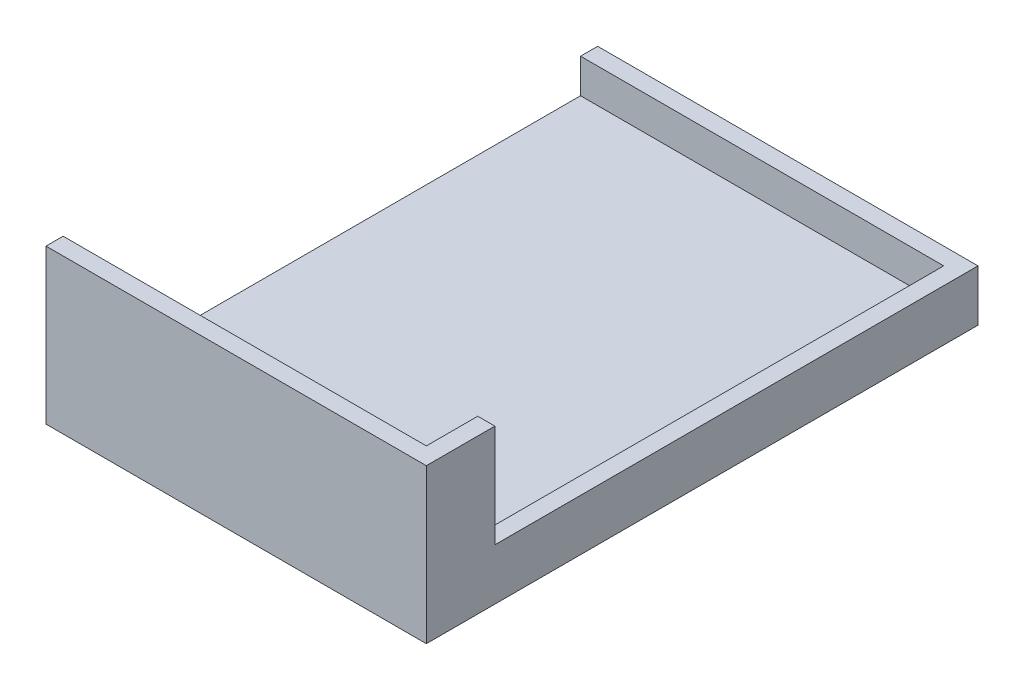
SolidWorks part; units mm, degrees
ref_plane "Front Plane" through (0, 0, 0) normal (0, 0, 1) x (1, 0, 0)
ref_plane "Top Plane" through (0, 0, 0) normal (0, 1, 0) x (1, 0, 0)
ref_plane "Right Plane" through (0, 0, 0) normal (1, 0, 0) x (0, 0, -1)
sketch "Sketch1" plane through (0, 0, 0) normal (0, 1, 0) x (1, 0, 0)
  line L1 (-31.635, -47.885) -> (32.5, -47.885) construction
  line L2 (-31.635, -47.885) -> (-31.635, 48) construction
  line L3 (-31.635, 48) -> (32.5, 48) construction
  line L4 (32.5, -47.885) -> (32.5, 48) construction
  line L5 (-34.81, -51.06) -> (35.675, -51.06)
  line L6 (-34.81, -51.06) -> (-34.81, 51.175)
  line L7 (-34.81, 51.175) -> (35.675, 51.175)
  line L8 (35.675, -51.06) -> (35.675, 51.175)
  point P0 (0, 0)
  point P6 (0, 0)
  dimension "D1" = 64.135
  dimension "D2" = 95.885
  dimension "D3" = 3.175
  dimension "D4" = 3.175
  dimension "D5" = 3.175
  dimension "D6" = 3.175
extrude "Boss-Extrude1" add sketch "Sketch1" along normal blind 28.575
shell "Shell1" thickness 3.175 removed face at (0.4325, 28.575, -0.0575) removed face at (-34.81, 14.2875, -0.0575)
sketch "Sketch2" plane through (35.675, 0, 0) normal (1, 0, 0) x (0, 0, -1)
  line L0 (-51.06, 28.575) -> (51.175, 28.575) construction
  line L1 (-38.36, 28.575) -> (51.175, 28.575)
  line L2 (-38.36, 28.575) -> (-38.36, 9.525)
  line L3 (-38.36, 9.525) -> (51.175, 9.525)
  line L4 (51.175, 28.575) -> (51.175, 9.525)
  line L5 (-51.06, 28.575) -> (-51.06, 0) construction
  line L6 (51.175, 28.575) -> (51.175, 0) construction
  dimension "D1" = 12.7
  dimension "D2" = 0
  dimension "D3" = 19.05
extrude "Cut-Extrude1" cut sketch "Sketch2" against normal up to surface (3.175 mm away) up to face at (32.5, 15.875, -0.0575)
sketch "Sketch3" plane through (0, 0, -51.175) normal (0, 0, -1) x (-1, 0, 0)
  line L0 (-35.675, 9.525) -> (-35.675, 0) construction
  line L1 (34.81, 28.575) -> (-32.5, 28.575)
  line L2 (34.81, 28.575) -> (34.81, 9.525)
  line L3 (34.81, 9.525) -> (-32.5, 9.525)
  line L4 (-32.5, 28.575) -> (-32.5, 9.525)
  dimension "D1" = 3.175
  dimension "D2" = 19.05
extrude "Cut-Extrude2" cut sketch "Sketch3" against normal up to surface (3.175 mm away) up to face at (5.576, 14.605, -48)
